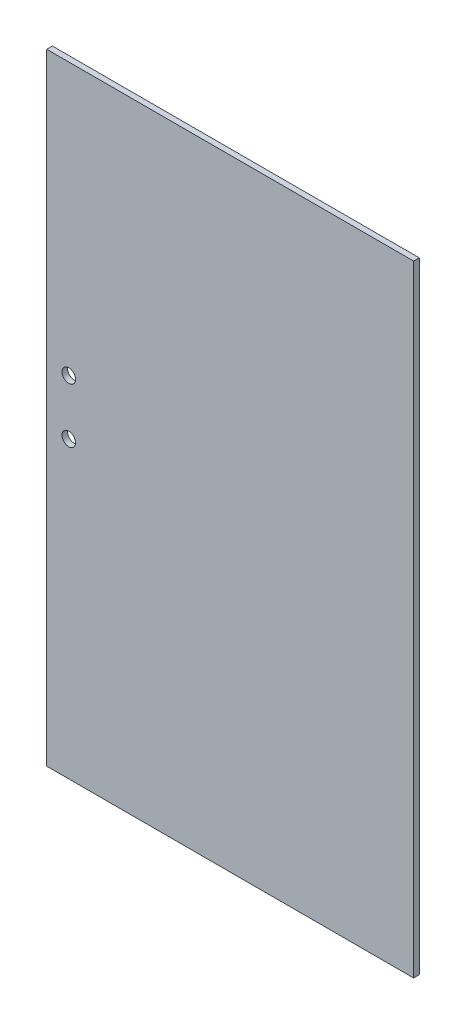
SolidWorks part; units mm, degrees
material "Oak"
ref_plane "Front Plane" through (0, 0, 0) normal (0, 0, 1) x (1, 0, 0)
ref_plane "Top Plane" through (0, 0, 0) normal (0, 1, 0) x (1, 0, 0)
ref_plane "Right Plane" through (0, 0, 0) normal (1, 0, 0) x (0, 0, -1)
sketch "Sketch1" plane through (0, 0, 0) normal (0, 0, 1) x (1, 0, 0)
  line L0 (0, 0) -> (0, 232.2316) construction
  line L1 (-162.5, 275) -> (162.5, 275)
  line L2 (-162.5, 275) -> (-162.5, -275)
  line L3 (-162.5, -275) -> (162.5, -275)
  line L4 (162.5, 275) -> (162.5, -275)
  line L5 (-162.5, 275) -> (162.5, -275) construction
  line L6 (-162.5, -275) -> (162.5, 275) construction
  circle A2 centre (-143, -14.218) radius 6
  circle A3 centre (-143, 34.4352) radius 6
  point P0 (0, 0)
  dimension "D1" = 550
  dimension "D2" = 325
base flange "Base-Flange1" sketch "Sketch1" thickness 5 reverse thickness direction no parameters "D1"=0.7366
sketch "Bend-Lines1" [suppressed] plane through (0, 0, 0) normal (0, 1, 0) x (1, 0, 0)
sketch "Bounding-Box1" [suppressed] plane through (0, 0, 0) normal (0, 1, 0) x (1, 0, 0)
sheet metal parameters "Sheet-Metal2" thickness 5 parameters "D1"=0.7366
flat pattern "Flat-Pattern2" [suppressed]
sketch "Bend-Lines2" plane through (0, 0, 0) normal (0, 1, 0) x (1, 0, 0)
sketch3d "Bounding-Box2" [suppressed]
  line L0 (162.5, 275, 0) -> (162.5, -275, 0) construction
  line L1 (-162.5, 275, 0) -> (-162.5, -275, 0) construction
  line L2 (162.5, 275, 0) -> (-162.5, 275, 0) construction
  line L3 (162.5, -275, 0) -> (-162.5, -275, 0) construction
